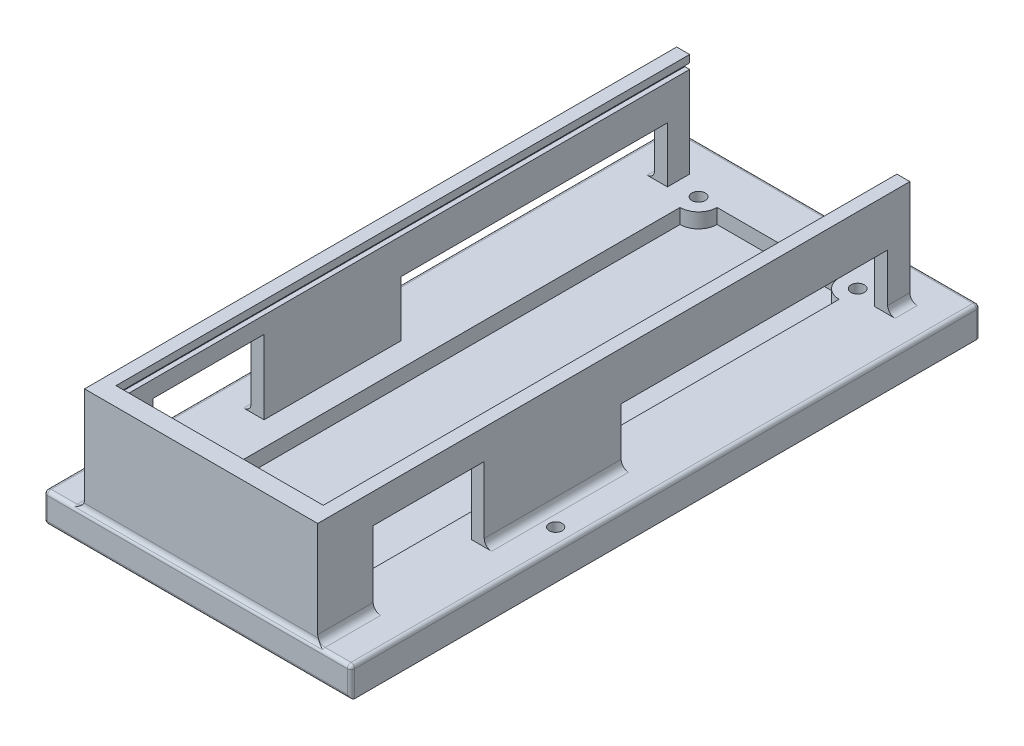
SolidWorks part; units mm, degrees
ref_plane "Front Plane" through (0, 0, 0) normal (0, 0, 1) x (1, 0, 0)
ref_plane "Top Plane" through (0, 0, 0) normal (0, 1, 0) x (1, 0, 0)
ref_plane "Right Plane" through (0, 0, 0) normal (1, 0, 0) x (0, 0, -1)
sketch "Sketch1" plane through (0, 0, 0) normal (0, 1, 0) x (1, 0, 0)
  line L0 (41.5, 95) -> (41.5, 0) construction
  line L1 (0, 0) -> (83, 0)
  line L2 (0, 0) -> (0, 170)
  line L3 (0, 170) -> (83, 170)
  line L4 (83, 0) -> (83, 170)
  line L5 (20, 156.9) -> (20, 13.1) construction
  circle A0 centre (5, 60.3) radius 1.75
  circle A1 centre (20, 13.1) radius 1.65 construction
  circle A2 centre (20, 156.9) radius 1.65 construction
  circle A3 centre (78, 60.3) radius 1.75
  circle A4 centre (63, 13.1) radius 1.65 construction
  circle A5 centre (63, 156.9) radius 1.65 construction
  point P19 (20, 85)
  point P20 (41.5, 0)
  point P21 (0, 85)
  dimension "D2" = 36.5
  dimension "D3" = 3.5
  dimension "D5" = 47.2
  dimension "D6" = 21.5
  dimension "D7" = 3.3
  dimension "D9" = 143.8
  dimension "D10" = 3.3
  dimension "D1" = 83
  dimension "D4" = 170
extrude "Boss-Extrude1" add sketch "Sketch1" along normal blind 8
sketch "Sketch3" plane through (0, 0, 0) normal (0, -1, 0) x (1, 0, 0)
  point P0 (20, -13.1)
  point P1 (63, -13.1)
  point P3 (63, -156.9)
  point P5 (20, -156.9)
hole_wizard "CBORE for M3 SHCS1" positions "Sketch3" profile "Sketch4" counterbore size "M3" standard "ANSI Metric" end condition through all
sketch "Sketch4" plane through (20, 0, -13.1) normal (1, 0, 0) x (0, 0, -1)
  line L0 (0, 0) -> (0, 8)
  line L1 (0, 8) -> (1.8, 8)
  line L3 (1.8, 8) -> (1.8, 3)
  line L4 (1.8, 3) -> (3.25, 3)
  line L5 (3.25, 3) -> (3.25, 0)
  line L7 (3.25, 0) -> (0, 0)
  line L11 (0, -6.35) -> (0, 107.95) construction
  dimension "Thru Hole Dia." = 3.6
  dimension "Thru Hole Depth" = 8
  dimension "C'Bore Dia." = 6.5
  dimension "C'Bore Depth" = 3
sketch "Sketch5" plane through (0, 8, 0) normal (0, 1, 0) x (1, 0, 0)
  line L5 (25, 156.9) -> (58, 156.9)
  line L6 (20, 151.9) -> (20, 18.1)
  line L11 (25, 13.1) -> (58, 13.1)
  line L12 (63, 151.9) -> (63, 18.1)
  arc A0 (20, 151.9) -> (25, 156.9) centre (20, 156.9) ccw
  arc A1 (58, 156.9) -> (63, 151.9) centre (63, 156.9) ccw
  arc A2 (63, 18.1) -> (58, 13.1) centre (63, 13.1) ccw
  arc A7 (25, 13.1) -> (20, 18.1) centre (20, 13.1) ccw
  point P0 (20, 156.9)
  point P1 (63, 156.9)
  point P2 (63, 13.1)
  point P3 (20, 13.1)
extrude "Cut-Extrude1" cut sketch "Sketch5" against normal blind 4
sketch "Sketch6" plane through (0, 0, 0) normal (0, -1, 0) x (1, 0, 0)
  line L1 (12, -95) -> (17, -95)
  line L2 (12, -95) -> (12, -115)
  line L3 (12, -115) -> (17, -115)
  line L4 (17, -95) -> (17, -115)
  dimension "D1" = 5
  dimension "D2" = 20
  dimension "D3" = 8
  dimension "D4" = 34.7
extrude "Boss-Extrude2" add sketch "Sketch6" along normal blind 8.8
sketch "Sketch7" plane through (0, 0, -115) normal (0, 0, -1) x (-1, 0, 0)
  line L0 (-17, -8.8) -> (-17, 0) construction
  line L1 (-12, 0) -> (-15.2, 0)
  line L2 (-12, 0) -> (-12, -6.8)
  line L3 (-12, -6.8) -> (-15.2, -6.8)
  line L4 (-15.2, 0) -> (-15.2, -6.8)
  dimension "D1" = 6.8
  dimension "D2" = 1.8
extrude "Cut-Extrude2" cut sketch "Sketch7" against normal through all
fillet "Fillet1" radius 6 1 edges at (17, 0, -105) second distance 8 first distance on face at (41.5, 0, -85)
fillet "Fillet2" radius 1 10 edges at (0, 4, 0) (41.5, 8, 0) (83, 4, 0) (83, 4, -170) (83, 8, -85) (41.5, 8, -170) (0, 4, -170) (0, 8, -85) (0, 0, -85) (41.5, 0, 0)
sketch "Sketch8" plane through (0, 8, 0) normal (0, 1, 0) x (1, 0, 0)
  line L1 (10, 161) -> (73, 161)
  line L2 (10, 161) -> (10, 1)
  line L3 (10, 1) -> (73, 1)
  line L4 (73, 161) -> (73, 1)
  line L6 (1, 1) -> (82, 1) construction
  circle A4 centre (5, 60.3) radius 1.75 construction
  dimension "D1" = 5
  dimension "D3" = 160
  dimension "D2" = 5
  dimension "D4" = 0
extrude "Boss-Extrude4" add sketch "Sketch8" along normal blind 28
sketch "Sketch11" plane through (0, 0, -161) normal (0, 0, -1) x (-1, 0, 0)
  line L0 (-73, 8) -> (-10, 8) construction
  line L1 (-69.5, 8) -> (-13.5, 8)
  line L2 (-69.5, 8) -> (-69.5, 32.5)
  line L3 (-69.5, 36) -> (-13.5, 36)
  line L4 (-13.5, 8) -> (-13.5, 32.5)
  line L5 (0, 0) -> (-83, 0) construction
  line L7 (-73, 36) -> (-10, 36) construction
  line L8 (-13.5, 32.5) -> (-12.2, 32.5)
  line L9 (-70.8, 34) -> (-69.5, 34)
  line L10 (-70.8, 34) -> (-70.8, 32.5)
  line L11 (-70.8, 32.5) -> (-69.5, 32.5)
  line L12 (-12.2, 34) -> (-12.2, 32.5)
  line L13 (-13.5, 34) -> (-12.2, 34)
  line L14 (-69.5, 34) -> (-69.5, 36)
  line L15 (-13.5, 34) -> (-13.5, 36)
  point P6 (-41.5, 36)
  point P9 (-41.5, 0)
  dimension "D1" = 56
  dimension "D2" = 1.3
  dimension "D3" = 0
  dimension "D5" = 1.5
  dimension "D6" = 1.3
  dimension "D7" = 2
extrude "Cut-Extrude3" cut sketch "Sketch11" against normal blind 155
sketch "Sketch12" plane through (0, 0, -6) normal (0, 0, -1) x (-1, 0, 0)
  line L1 (-70.8, 34) -> (-12.2, 34)
  line L2 (-70.8, 34) -> (-70.8, 32.5)
  line L3 (-70.8, 32.5) -> (-12.2, 32.5)
  line L4 (-12.2, 34) -> (-12.2, 32.5)
extrude "Cut-Extrude4" cut sketch "Sketch12" against normal blind 1
sketch "Sketch15" plane through (73, 0, 0) normal (1, 0, 0) x (0, 0, -1)
  line L0 (1, 8) -> (169, 8) construction
  line L1 (128, 8) -> (110, 8)
  line L2 (128, 8) -> (128, 23) construction
  line L3 (128, 23) -> (110, 23)
  line L4 (110, 8) -> (110, 23) construction
  line L5 (101, 23) -> (110, 23)
  line L6 (1, 8) -> (161, 8) construction
  line L7 (101, 8) -> (83, 8)
  line L8 (101, 8) -> (101, 23) construction
  line L9 (101, 23) -> (83, 23)
  line L10 (83, 8) -> (83, 23)
  line L12 (101, 8) -> (110, 8)
  line L13 (128, 23) -> (137, 23)
  line L14 (137, 23) -> (155, 23)
  line L15 (137, 23) -> (137, 8) construction
  line L16 (137, 8) -> (155, 8)
  line L17 (155, 23) -> (155, 8)
  line L18 (128, 8) -> (137, 8)
  line L20 (161, 36) -> (161, 8) construction
  dimension "D1" = 18
  dimension "D2" = 15
  dimension "D3" = 6
  dimension "D4" = 18
  dimension "D5" = 15
  dimension "D6" = 9
  dimension "D7" = 18
  dimension "D8" = 15
  dimension "D9" = 9
extrude "Cut-Extrude5" cut sketch "Sketch15" against normal through all and the other way through all
sketch "Sketch16" plane through (73, 0, 0) normal (1, 0, 0) x (0, 0, -1)
  line L0 (1, 8) -> (169, 8) construction
  line L1 (16, 8) -> (46, 8)
  line L2 (16, 8) -> (16, 28)
  line L3 (16, 28) -> (46, 28)
  line L4 (46, 8) -> (46, 28)
  line L5 (1, 36) -> (1, 8) construction
  point P8 (16, 18)
  dimension "D1" = 20
  dimension "D2" = 30
  dimension "D3" = 15
extrude "Cut-Extrude6" cut sketch "Sketch16" against normal through all
sketch "Sketch17" plane through (0, 36, 0) normal (0, 1, 0) x (1, 0, 0)
  circle A0 centre (5, 60.3) radius 3
  circle A1 centre (78, 60.3) radius 3
extrude "Cut-Extrude7" [suppressed] cut sketch "Sketch17" against normal up to surface (28 mm away) up to face at (41.5, 8, -85)
fillet "Fillet3" radius 2 7 edges at (10, 8, -158) (10, 8, -64.5) (10, 8, -8.5) (41.5, 8, -1) (73, 8, -158) (73, 8, -64.5) (73, 8, -8.5)
